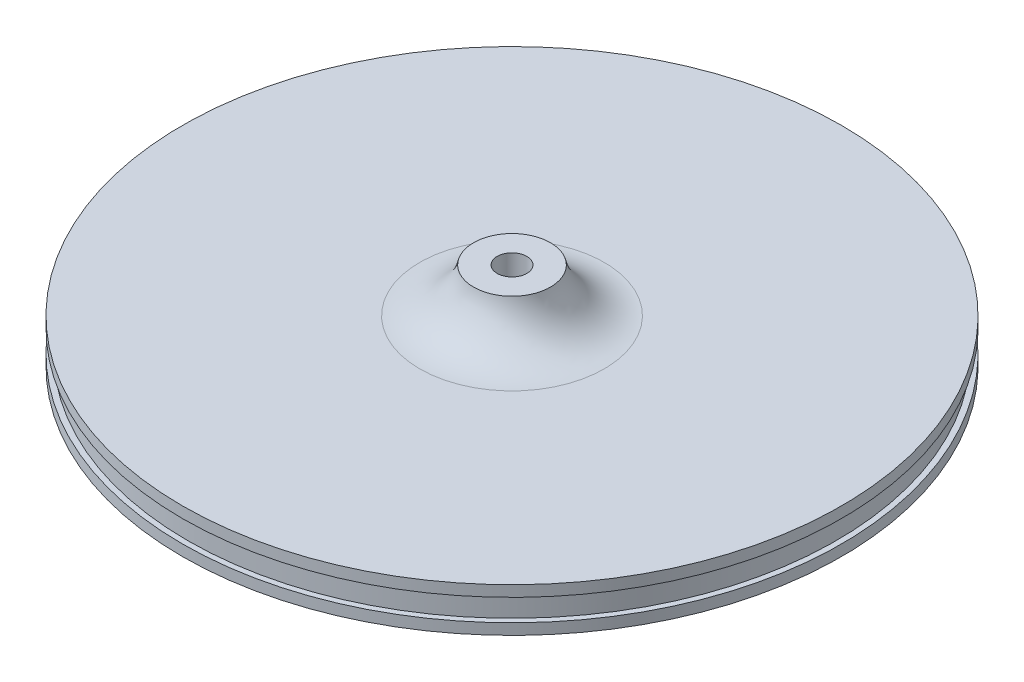
SolidWorks part; units mm, degrees
ref_plane "Front Plane" through (0, 0, 0) normal (0, 0, 1) x (1, 0, 0)
ref_plane "Top Plane" through (0, 0, 0) normal (0, 1, 0) x (1, 0, 0)
ref_plane "Right Plane" through (0, 0, 0) normal (1, 0, 0) x (0, 0, -1)
sketch "Sketch1" plane through (0, 0, 0) normal (0, 1, 0) x (1, 0, 0)
  circle A0 centre (0, 0) radius 30
  circle A1 centre (0, 0) radius 3.5
  circle A2 centre (0, 0) radius 1.35
  dimension "D1" = 2.7
  dimension "D2" = 60
  dimension "D3" = 7
extrude "Boss-Extrude1" add sketch "Sketch1" along normal blind 4 contours A2 | A0 region at (0, 0, 0)
extrude "Boss-Extrude2" add sketch "Sketch1<3>" along normal blind 8 contours A1 A2 region at (-3.401, 0, 0)
sketch "Sketch1<3>" plane through (0, 0, 0) normal (0, 1, 0) x (1, 0, 0) same geometry as "Sketch1"
fillet "Fillet1" radius 5 1 edges at (0, 4, 3.5)
sketch "Sketch2" plane through (0, 0, 0) normal (0, 0, 1) x (1, 0, 0)
  line L0 (30, 0) -> (30, 4) construction
  line L1 (30, 3) -> (29.5, 3)
  line L2 (30, 3) -> (30, 1)
  line L3 (30, 1) -> (29.5, 1)
  line L4 (29.5, 3) -> (29.5, 1)
  line L5 (30, 4) -> (-30, 4) construction
  line L6 (-30, 0) -> (30, 0) construction
  dimension "D1" = 1
  dimension "D2" = 1
  dimension "D3" = 0.5
revolve "Cut-Revolve1" cut sketch "Sketch2" angle 360 about axis through (0, 4, 0) along (0, -1, 0)
